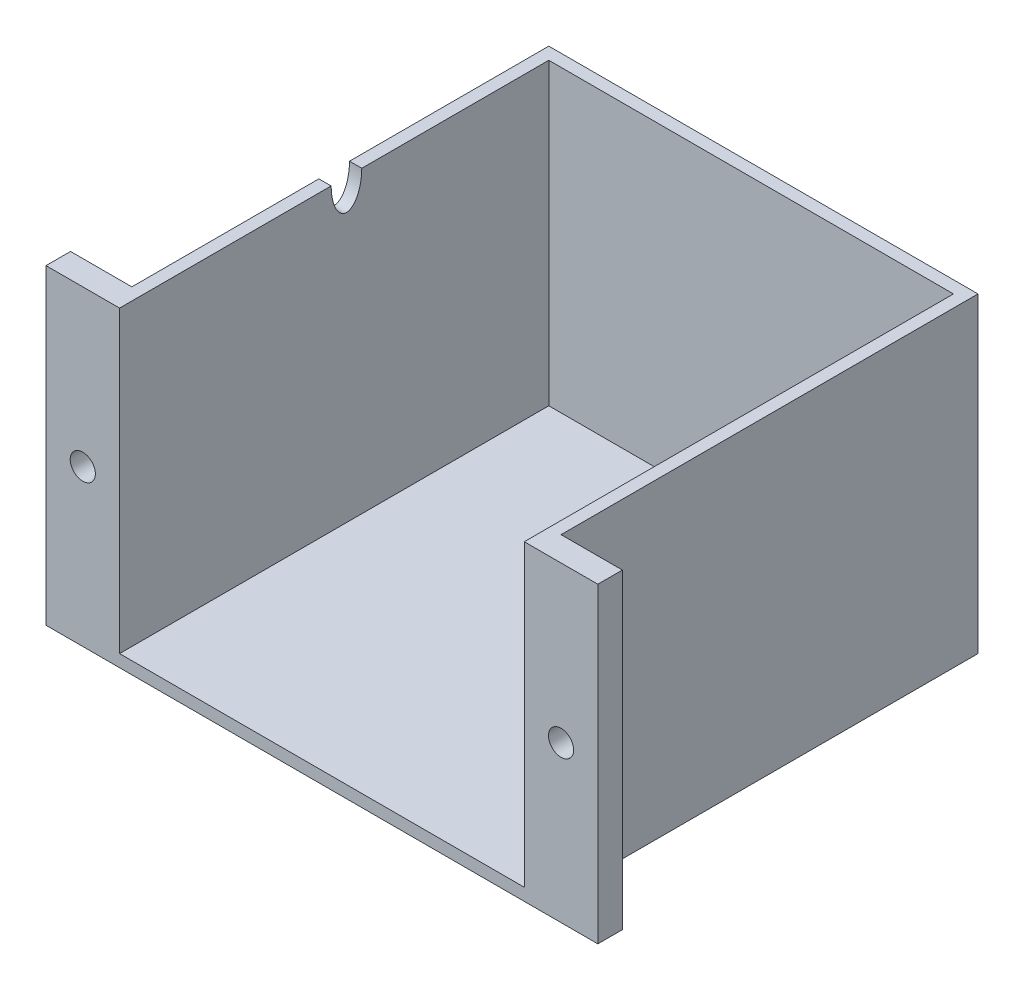
SolidWorks part; units mm, degrees
ref_plane "Front Plane" through (0, 0, 0) normal (0, 0, 1) x (1, 0, 0)
ref_plane "Top Plane" through (0, 0, 0) normal (0, 1, 0) x (1, 0, 0)
ref_plane "Right Plane" through (0, 0, 0) normal (1, 0, 0) x (0, 0, -1)
sketch "Sketch1" plane through (0, 0, 0) normal (0, 1, 0) x (1, 0, 0)
  line L0 (-10, 0) -> (0, 0)
  line L1 (0, 0) -> (0, 68)
  line L2 (0, 68) -> (70, 68)
  line L3 (70, 68) -> (70, 0)
  line L4 (70, 0) -> (80, 0)
  line L5 (80, 0) -> (80, -4)
  line L6 (80, -4) -> (68, -4)
  line L7 (68, -4) -> (68, 66)
  line L8 (68, 66) -> (2, 66)
  line L9 (2, 66) -> (2, -4)
  line L10 (2, -4) -> (-10, -4)
  line L11 (-10, -4) -> (-10, 0)
  dimension "D2" = 2
  dimension "D3" = 2
  dimension "D4" = 2
  dimension "D5" = 70
  dimension "D6" = 10
  dimension "D7" = 70
extrude "Boss-Extrude1" add sketch "Sketch1" along normal blind 50.8
sketch "CableHoleSketch2" plane through (2, 0, 0) normal (1, 0, 0) x (0, 0, -1)
  line L0 (0, 50.8) -> (68, 50.8) construction
  line L2 (30.5, 50.8) -> (35.5, 50.8)
  ellipse E0 centre (33, 50.8) end of major axis (33, 45.8) minor radius 2.5 (30.5, 50.8) -> (35.5, 50.8) ccw
  dimension "D1" = 35
  dimension "D2" = 5
  dimension "D3" = 5
extrude "CableHoleCut-Extrude1" cut sketch "CableHoleSketch2" against normal through all
sketch "BottomCoverSketch3" plane through (0, 0, -66) normal (0, 0, 1) x (1, 0, 0)
  line L0 (2, 0) -> (68, 0) construction
  line L1 (2, 0) -> (68, 0)
  line L2 (2, 0) -> (2, 2)
  line L3 (2, 2) -> (68, 2)
  line L4 (68, 0) -> (68, 2)
  line L5 (68, 50.8) -> (68, 0) construction
  line L6 (2, 50.8) -> (2, 0) construction
extrude "BottomCoverBoss-Extrude2" add sketch "BottomCoverSketch3" along normal blind 70
sketch "MountingHolesSketch4" plane through (0, 0, 4) normal (0, 0, 1) x (1, 0, 0)
  line L0 (68, 50.8) -> (80, 0) construction
  line L1 (-10, 0) -> (2, 50.8) construction
  circle A0 centre (74, 25.4) radius 2.05
  circle A1 centre (-4, 25.4) radius 2.05
  dimension "D1" = 4.1
extrude "MountingHolesCut-Extrude2" cut sketch "MountingHolesSketch4" against normal blind 4
equation "\"PowerSwitchCoverWallThickness\"=2"
equation "\"PowerSwitchCoverWidth\"= 70mm"
equation "\"PowerSwitchCoverHeight\"= 50.8mm"
equation "\"PowerSwitchCoverTabWidth\"= 10mm"
equation "\"D1@BottomCoverSketch3\" = \"PowerSwitchCoverWallThickness\""
equation "\"D1@BottomCoverBoss-Extrude2\" = \"PowerSwitchCoverWidth\""
equation "\"PowerSwitchCoverLength\"= 70mm"
equation "\"D7@Sketch1\"=\"PowerSwitchCoverLength\""
equation "\"D5@Sketch1\"=\"PowerSwitchCoverWidth\""
equation "\"D3@Sketch1\"=\"PowerSwitchCoverWallThickness\""
equation "\"D1@Sketch1\"=\"M3HeatInsertHoleDepth\""
equation "\"D4@Sketch1\"=\"PowerSwitchCoverWallThickness\""
equation "\"D6@Sketch1\"=\"PowerSwitchCoverTabWidth\""
equation "\"M3HeatInsertHoleDiameter\"= 4mm + .1mm'Add .1mm for printing"
equation "\"M3HeatInsertHoleDepth\"= 4mm"
equation "\"D1@MountingHolesSketch4\"=\"M3HeatInsertHoleDiameter\""
equation "\"D2@Sketch1\"=\"PowerSwitchCoverWallThickness\""
equation "\"D1@Boss-Extrude1\"=\"PowerSwitchCoverHeight\""
